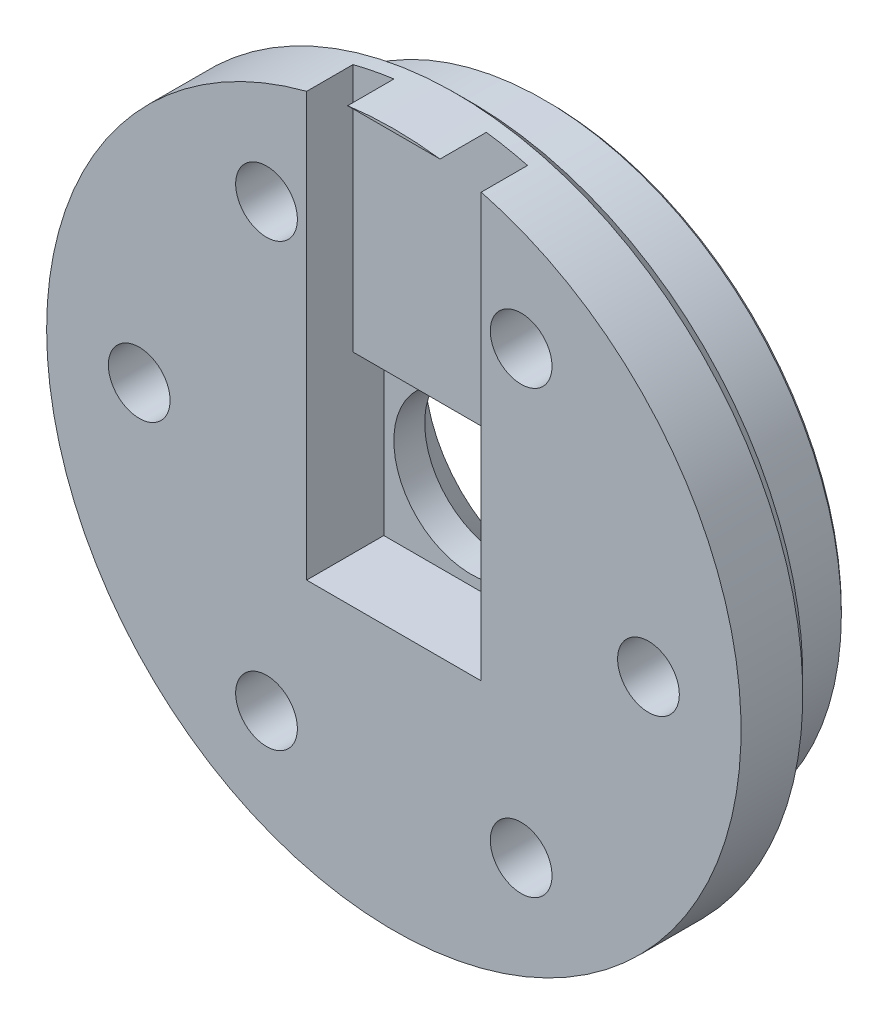
SolidWorks part; units mm, degrees
ref_plane "Front Plane" through (0, 0, 0) normal (0, 0, 1) x (1, 0, 0)
ref_plane "Top Plane" through (0, 0, 0) normal (0, 1, 0) x (1, 0, 0)
ref_plane "Right Plane" through (0, 0, 0) normal (1, 0, 0) x (0, 0, -1)
sketch "Sketch1" plane through (0, 0, 0) normal (0, 0, 1) x (1, 0, 0)
  circle A0 centre (0, 0) radius 9.8
  circle A1 centre (0, 0) radius 5
  dimension "D1" = 19.6
  dimension "D2" = 10
extrude "Boss-Extrude1" add sketch "Sketch1" along normal blind 10
sketch "Sketch2" plane through (0, 0, 10) normal (0, 0, 1) x (1, 0, 0)
  line L1 (-5.65, 5.65) -> (5.65, 5.65)
  line L2 (-5.65, 5.65) -> (-5.65, -5.65)
  line L3 (-5.65, -5.65) -> (5.65, -5.65)
  line L4 (5.65, 5.65) -> (5.65, -5.65)
  point P4 (5.65, 0)
  point P5 (0, 5.65)
  dimension "D1" = 11.3
  dimension "D2" = 11.3
extrude "Cut-Extrude1" cut sketch "Sketch2" against normal blind 5
sketch "Sketch3" plane through (0, 0, 10) normal (0, 0, 1) x (1, 0, 0)
  line L1 (-5.65, 5.65) -> (5.6634, 5.65)
  line L2 (-5.65, 5.65) -> (-5.65, 10.3571)
  line L3 (-5.65, 10.3571) -> (5.6634, 10.3571)
  line L4 (5.6634, 5.65) -> (5.6634, 10.3571)
extrude "Cut-Extrude2" cut sketch "Sketch3" against normal blind 3
sketch "Sketch4" plane through (0, 0, 10) normal (0, 0, 1) x (1, 0, 0)
  line L1 (-13.2922, 9.0382) -> (-7.8874, 9.0382)
  line L2 (-13.2922, 9.0382) -> (-13.2922, -9.0382)
  line L3 (-13.2922, -9.0382) -> (-7.8874, -9.0382)
  line L4 (-7.8874, 9.0382) -> (-7.8874, -9.0382)
  line L5 (13.4474, 9.0382) -> (7.784, 9.0382)
  line L6 (13.4474, 9.0382) -> (13.4474, -8.9089)
  line L7 (13.4474, -8.9089) -> (7.784, -8.9089)
  line L8 (7.784, 9.0382) -> (7.784, -8.9089)
extrude "Cut-Extrude3" cut sketch "Sketch4" against normal blind 3
chamfer "Chamfer1" distance 3 angle 45 1 edges at (5, 0, 0)
ref_plane "Plane1" through (0, 0, 5) normal (0, 0, -1) x (-1, 0, 0)
sketch "Sketch5" plane through (0, 0, 5) normal (0, 0, -1) x (-1, 0, 0)
  circle A0 centre (0, 0) radius 9.8
  circle A1 centre (0, 0) radius 22.5
  dimension "D1" = 12.7
extrude "Boss-Extrude2" add sketch "Sketch5" against normal blind 1
sketch "Sketch6" plane through (0, 0, 5) normal (0, 0, -1) x (-1, 0, 0)
  circle A0 centre (0, 0) radius 9.8
  circle A1 centre (0, 0) radius 11.25
  dimension "D1" = 22.5
extrude "Boss-Extrude3" add sketch "Sketch6" along normal up to surface (5 mm away) up to face at (8, 0, 0)
sketch "Sketch7" plane through (0, 0, 5) normal (0, 0, -1) x (-1, 0, 0)
  circle A0 centre (0, 0) radius 18.75
  circle A1 centre (0, 0) radius 19.25
  dimension "D1" = 37.5
  dimension "D2" = 38.5
extrude "Boss-Extrude4" add sketch "Sketch7" along normal up to surface (5 mm away) up to face at (8, 0, 0)
chamfer "Chamfer2" distance 0.25 angle 45 1 edges at (19.25, 0, 0)
sketch "Sketch9" plane through (0, 0, 6) normal (0, 0, 1) x (1, 0, 0)
  circle A0 centre (0, 0) radius 22.5
  circle A1 centre (0, 0) radius 9.8
  circle A2 centre (0, 0) radius 9.8 construction
  circle A3 centre (0, 0) radius 22.5 construction
extrude "Boss-Extrude5" add sketch "Sketch9" along normal up to surface (4 mm away) up to face at (1.1075, 1.2261, 10)
sketch "Sketch10" plane through (0, 0, 10) normal (0, 0, 1) x (1, 0, 0)
  line L1 (-5.65, 5.65) -> (5.6634, 5.65)
  line L2 (-5.65, 5.65) -> (-5.65, 22.3)
  line L3 (-5.65, 22.3) -> (5.6634, 22.3)
  line L4 (5.6634, 5.65) -> (5.6634, 22.3)
extrude "Cut-Extrude5" cut sketch "Sketch10" against normal up to surface (3 mm away) up to face at (1.1357, 6.9505, 7)
sketch "Sketch8" plane through (0, 0, 5) normal (0, 0, -1) x (-1, 0, 0)
  circle A0 centre (-8.25, 14.2894) radius 2
  dimension "D1" = 4
extrude "Cut-Extrude4" cut sketch "Sketch8" against normal through all
ref_axis "Axis1" through (0, 0, 10.5849) along (0, 0, -1)
pattern_circular "CirPattern1" count 6 over 360 about axis through (0, 0, 10.5849) along (0, 0, -1) of "Cut-Extrude4"
sketch "Sketch12" plane through (0, 0, 7) normal (0, 0, 1) x (1, 0, 0)
  line L1 (-9.9396, 6.8335) -> (-7.0029, 6.8335)
  line L2 (-9.9396, 6.8335) -> (-9.9396, -6.3817)
  line L3 (-9.9396, -6.3817) -> (-7.0029, -6.3817)
  line L4 (-7.0029, 6.8335) -> (-7.0029, -6.3817)
  line L5 (6.8899, 6.9464) -> (10.222, 6.9464)
  line L6 (6.8899, 6.9464) -> (6.8899, -6.3817)
  line L7 (6.8899, -6.3817) -> (10.222, -6.3817)
  line L8 (10.222, 6.9464) -> (10.222, -6.3817)
extrude "Boss-Extrude6" add sketch "Sketch12" along normal up to surface (3 mm away) up to face at (15.5, 1.7321, 10)
chamfer "Chamfer3" distance 1 angle 45 1 edges at (-22.5, 0, 5)
